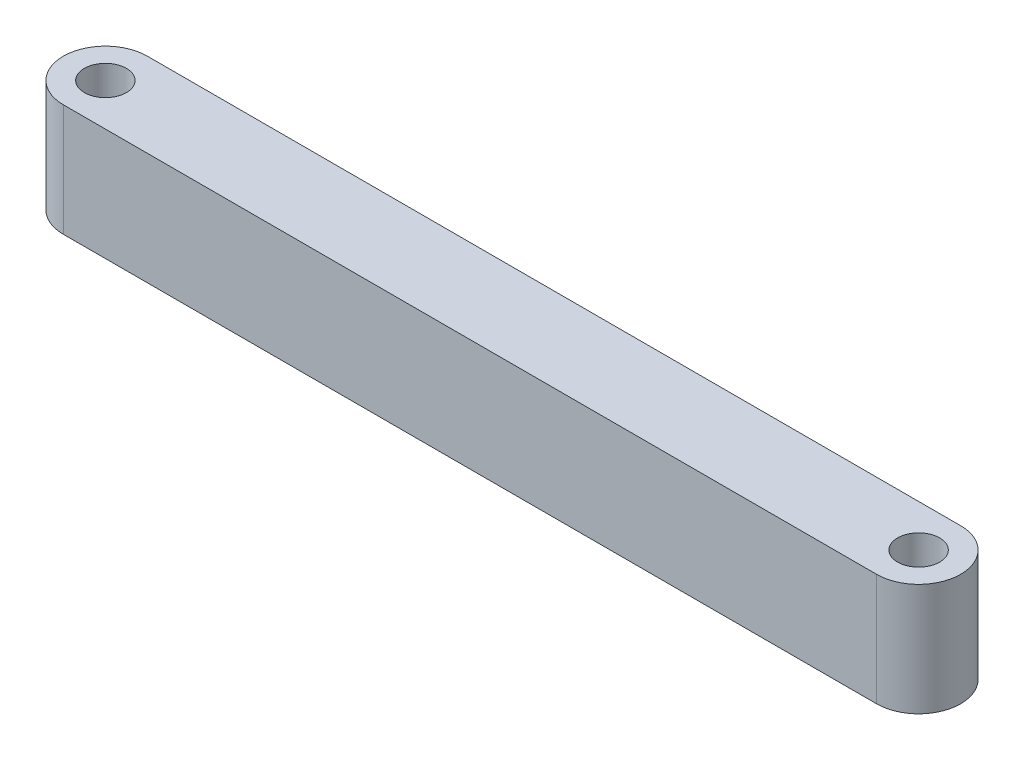
SolidWorks part; units mm, degrees
ref_plane "Alzado" through (0, 0, 0) normal (0, 0, 1) x (1, 0, 0)
ref_plane "Planta" through (0, 0, 0) normal (0, 1, 0) x (1, 0, 0)
ref_plane "Vista lateral" through (0, 0, 0) normal (1, 0, 0) x (0, 0, -1)
sketch "Croquis1" plane through (0, 0, 0) normal (0, 1, 0) x (1, 0, 0)
  line L0 (-14.5, 0) -> (14.5, 0) construction
  line L7 (-14.5, 1.5) -> (14.5, 1.5)
  line L8 (14.5, -1.5) -> (-14.5, -1.5)
  circle A0 centre (14.5, 0) radius 0.75
  circle A1 centre (-14.5, 0) radius 0.75
  arc A2 (14.5, -1.5) -> (14.5, 1.5) centre (14.5, 0) ccw
  arc A3 (-14.5, 1.5) -> (-14.5, -1.5) centre (-14.5, 0) ccw
  point P0 (0, 0)
  dimension "D2" = 1.5
  dimension "D3" = 3
  dimension "D1" = 29
extrude "Saliente-Extruir1" add sketch "Croquis1" along normal blind 4
